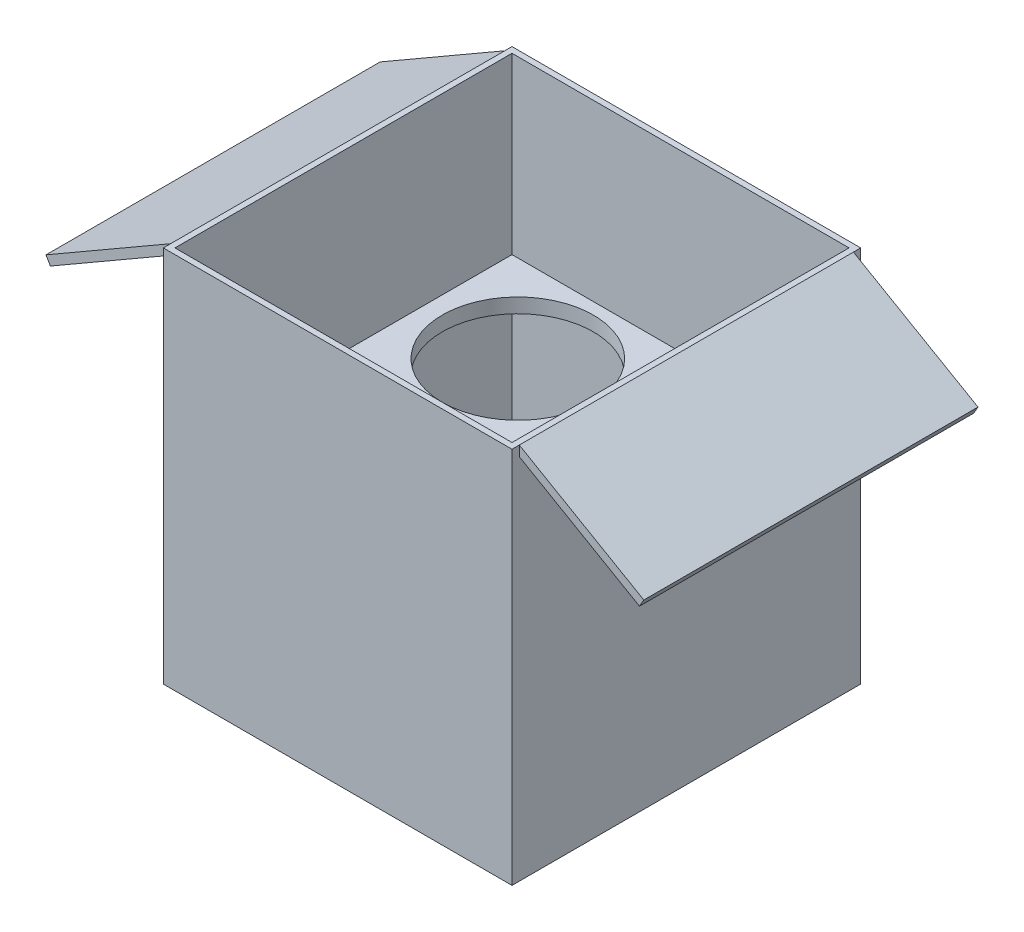
SolidWorks part; units mm, degrees
ref_plane "Front Plane" through (0, 0, 0) normal (0, 0, 1) x (1, 0, 0)
ref_plane "Top Plane" through (0, 0, 0) normal (0, 1, 0) x (1, 0, 0)
ref_plane "Right Plane" through (0, 0, 0) normal (1, 0, 0) x (0, 0, -1)
sketch "Sketch1" plane through (0, 0, 0) normal (0, 1, 0) x (1, 0, 0)
  line L0 (-58, 58) -> (58, 58)
  line L1 (-60, 60) -> (60, 60)
  line L2 (-60, 60) -> (-60, -60)
  line L3 (-60, -60) -> (60, -60)
  line L4 (60, 60) -> (60, -60)
  line L5 (-60, 60) -> (60, -60) construction
  line L6 (-60, -60) -> (60, 60) construction
  line L7 (58, 58) -> (58, -58)
  line L8 (-58, -58) -> (58, -58)
  line L9 (-58, 58) -> (-58, -58)
  point P0 (0, 0)
  dimension "D1" = 120
  dimension "D2" = 2
extrude "Boss-Extrude1" add sketch "Sketch1" along normal blind 5 contours L4 L1 L2 L3 L9 L0 L7 L8 | L0 L7 L8 L9 region at (0, 0, -58.3029)
extrude "Boss-Extrude2" add sketch "Sketch1<3>" along normal blind 130
sketch "Sketch1<3>" plane through (0, 0, 0) normal (0, 1, 0) x (1, 0, 0) same geometry as "Sketch1"
sketch "Sketch2" plane through (0, 0, 0) normal (0, 0, 1) x (1, 0, 0)
  line L0 (60, 130) -> (102.8683, 105.25)
  line L1 (102.8683, 105.25) -> (101.3683, 102.6519)
  line L2 (101.3683, 102.6519) -> (60, 126.5359)
  line L3 (60, 130) -> (60, 0) construction
  line L4 (60, 126.5359) -> (60, 130)
  dimension "D1" = 60
  dimension "D2" = 49.5
  dimension "D3" = 3
extrude "Boss-Extrude3" add sketch "Sketch2" along normal mid plane 115
mirror "Mirror1" about plane through (0, 0, 0) normal (1, 0, 0) of "Boss-Extrude3"
ref_plane "Plane1" through (0, 130, 0) normal (0, 1, 0) x (1, 0, 0)
sketch "Sketch3" plane through (0, 130, 0) normal (0, 1, 0) x (1, 0, 0)
  point P0 (0, 0)
sketch "Sketch4" plane through (0, 0, -58) normal (0, 0, 1) x (1, 0, 0)
  line L0 (60, 130) -> (60, 0) construction
  line L1 (-60, 65) -> (60, 65)
  line L2 (-60, 65) -> (-60, 70)
  line L3 (-60, 70) -> (60, 70)
  line L4 (60, 65) -> (60, 70)
  line L5 (-60, 65) -> (60, 70) construction
  line L6 (-60, 70) -> (60, 65) construction
  point P0 (0, 67.5)
  dimension "D1" = 5
  dimension "D2" = 65
extrude "Boss-Extrude4" add sketch "Sketch4" along normal up to surface (118 mm away) up to face at (0, 65, 60)
sketch "Sketch5" plane through (0, 70, 0) normal (0, 1, 0) x (1, 0, 0)
  line L0 (58, 58) -> (-58, 58) construction
  line L1 (-58, 58) -> (58, 58) construction
  circle A0 centre (28, 28) radius 26
  circle A1 centre (-26, 28) radius 26
  circle A2 centre (28, -28) radius 26
  circle A3 centre (-26, -28) radius 26
  point P12 (0, 0)
  dimension "D2" = 52
  dimension "D3" = 52
  dimension "D4" = 30
  dimension "D5" = 30
  dimension "D1" = 54
extrude "Cut-Extrude1" cut sketch "Sketch5" against normal blind 10
